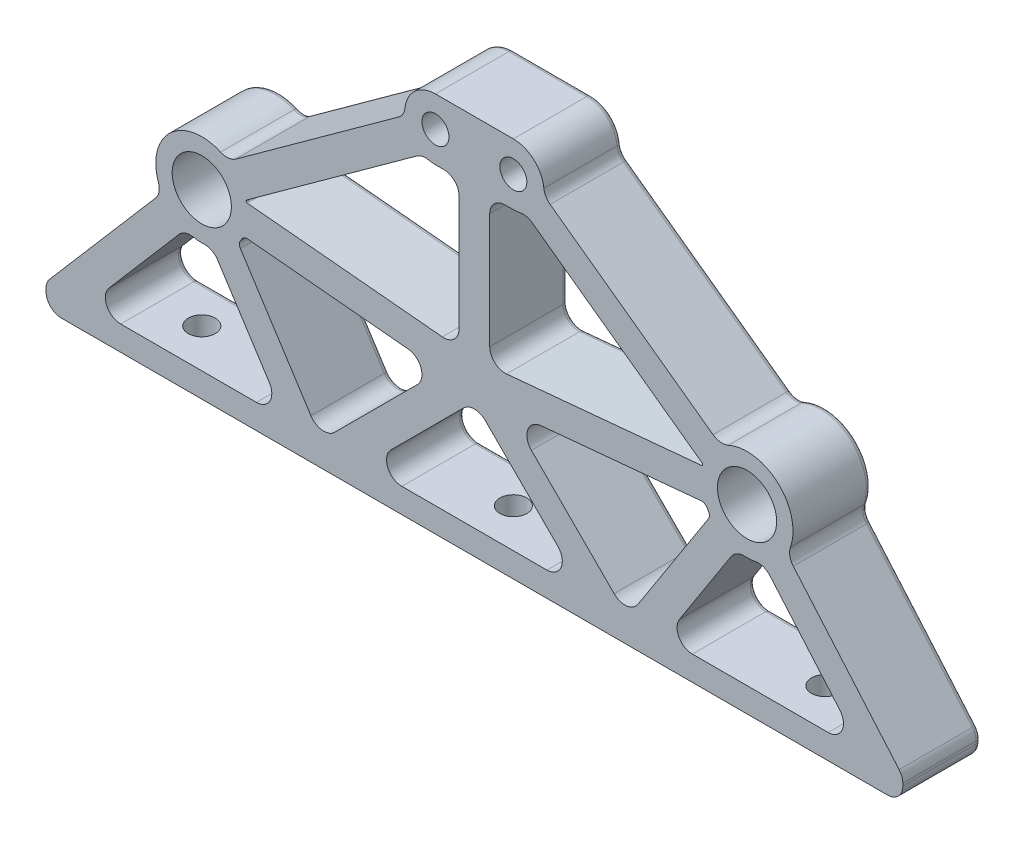
SolidWorks part; units mm, degrees
note: The reader was unsure of these and kept them because the rebuilt part matched: shared geometry of "Sketch3<3>".
ref_plane "Front Plane" through (0, 0, 0) normal (0, 0, 1) x (1, 0, 0)
ref_plane "Top Plane" through (0, 0, 0) normal (0, 1, 0) x (1, 0, 0)
ref_plane "Right Plane" through (0, 0, 0) normal (1, 0, 0) x (0, 0, -1)
sketch "Sketch1" plane through (0, 0, 0) normal (0, 0, 1) x (1, 0, 0)
  line L0 (0, 0) -> (60.4965, 0) construction
  circle A0 centre (0, 0) radius 25.4 construction
  circle A1 centre (44.45, 35.921) radius 31.75 construction
  circle A2 centre (133.35, 35.921) radius 31.75 construction
  circle A3 centre (177.8, 0) radius 25.4 construction
  circle A4 centre (222.25, 35.921) radius 31.75 construction
  circle A5 centre (311.15, 35.921) radius 31.75 construction
  circle A6 centre (355.6, 0) radius 25.4 construction
  circle A7 centre (0, 0) radius 50.8 construction
  circle A8 centre (355.6, 0) radius 50.8 construction
  circle A9 centre (177.8, 0) radius 50.8 construction
  circle A10 centre (88.9, 35.921) radius 12.7 construction
  circle A11 centre (266.7, 35.921) radius 12.7 construction
  point P20 (-50.8, 0)
  point P21 (406.4, 0)
  dimension "D1" = 50.8
  dimension "D2" = 63.5
  dimension "D4" = 101.6
  dimension "D5" = 25.4
  dimension "D6" = 25.4
  dimension "D3" = 355.6
  dimension "D7" = 177.8
  dimension "D8" = 177.8
  dimension "D9" = 457.2
  dimension "D10" = 44.45
sketch "Sketch2" plane through (0, 0, 0) normal (0, 0, 1) x (1, 0, 0)
  line L0 (-200000, 0) -> (200060.4965, 0) construction
  line L1 (-44.45, 6.35) -> (400.05, 6.35) construction
  line L2 (-44.45, 6.35) -> (-44.45, -19.05) construction
  line L3 (-44.45, -19.05) -> (400.05, -19.05) construction
  line L4 (400.05, 6.35) -> (400.05, -19.05) construction
  circle A0 centre (-38.1, 0) radius 2.25 construction
  circle A2 centre (-31.75, -6.35) radius 2.25 construction
  circle A3 centre (-25.4, 0) radius 2.25 construction
  circle A4 centre (-12.7, 0) radius 2.25 construction
  circle A5 centre (0, 0) radius 2.25 construction
  circle A6 centre (12.7, 0) radius 2.25 construction
  circle A7 centre (25.4, 0) radius 2.25 construction
  circle A8 centre (38.1, 0) radius 2.25 construction
  circle A9 centre (50.8, 0) radius 2.25 construction
  circle A10 centre (63.5, 0) radius 2.25 construction
  circle A11 centre (76.2, 0) radius 2.25 construction
  circle A12 centre (88.9, 0) radius 2.25 construction
  circle A13 centre (101.6, 0) radius 2.25 construction
  circle A14 centre (114.3, 0) radius 2.25 construction
  circle A15 centre (127, 0) radius 2.25 construction
  circle A16 centre (139.7, 0) radius 2.25 construction
  circle A17 centre (152.4, 0) radius 2.25 construction
  circle A18 centre (165.1, 0) radius 2.25 construction
  circle A19 centre (177.8, 0) radius 2.25 construction
  circle A20 centre (190.5, 0) radius 2.25 construction
  circle A21 centre (203.2, 0) radius 2.25 construction
  circle A22 centre (215.9, 0) radius 2.25 construction
  circle A23 centre (228.6, 0) radius 2.25 construction
  circle A24 centre (241.3, 0) radius 2.25 construction
  circle A25 centre (254, 0) radius 2.25 construction
  circle A26 centre (266.7, 0) radius 2.25 construction
  circle A27 centre (279.4, 0) radius 2.25 construction
  circle A28 centre (292.1, 0) radius 2.25 construction
  circle A29 centre (304.8, 0) radius 2.25 construction
  circle A30 centre (317.5, 0) radius 2.25 construction
  circle A31 centre (330.2, 0) radius 2.25 construction
  circle A32 centre (342.9, 0) radius 2.25 construction
  circle A33 centre (355.6, 0) radius 2.25 construction
  circle A34 centre (368.3, 0) radius 2.25 construction
  circle A35 centre (381, 0) radius 2.25 construction
  circle A36 centre (393.7, 0) radius 2.25 construction
  circle A37 centre (-25.4, -12.7) radius 2.25 construction
  circle A38 centre (-12.7, -12.7) radius 2.25 construction
  circle A39 centre (0, -12.7) radius 2.25 construction
  circle A40 centre (12.7, -12.7) radius 2.25 construction
  circle A41 centre (25.4, -12.7) radius 2.25 construction
  circle A42 centre (38.1, -12.7) radius 2.25 construction
  circle A43 centre (50.8, -12.7) radius 2.25 construction
  circle A44 centre (63.5, -12.7) radius 2.25 construction
  circle A45 centre (76.2, -12.7) radius 2.25 construction
  circle A46 centre (88.9, -12.7) radius 2.25 construction
  circle A47 centre (101.6, -12.7) radius 2.25 construction
  circle A48 centre (114.3, -12.7) radius 2.25 construction
  circle A49 centre (127, -12.7) radius 2.25 construction
  circle A50 centre (139.7, -12.7) radius 2.25 construction
  circle A51 centre (152.4, -12.7) radius 2.25 construction
  circle A52 centre (165.1, -12.7) radius 2.25 construction
  circle A53 centre (177.8, -12.7) radius 2.25 construction
  circle A54 centre (190.5, -12.7) radius 2.25 construction
  circle A55 centre (203.2, -12.7) radius 2.25 construction
  circle A56 centre (215.9, -12.7) radius 2.25 construction
  circle A57 centre (228.6, -12.7) radius 2.25 construction
  circle A58 centre (241.3, -12.7) radius 2.25 construction
  circle A59 centre (254, -12.7) radius 2.25 construction
  circle A60 centre (266.7, -12.7) radius 2.25 construction
  circle A61 centre (279.4, -12.7) radius 2.25 construction
  circle A62 centre (292.1, -12.7) radius 2.25 construction
  circle A63 centre (304.8, -12.7) radius 2.25 construction
  circle A64 centre (317.5, -12.7) radius 2.25 construction
  circle A65 centre (330.2, -12.7) radius 2.25 construction
  circle A66 centre (342.9, -12.7) radius 2.25 construction
  circle A67 centre (355.6, -12.7) radius 2.25 construction
  circle A68 centre (368.3, -12.7) radius 2.25 construction
  circle A69 centre (381, -12.7) radius 2.25 construction
  circle A70 centre (393.7, -12.7) radius 2.25 construction
  circle A71 centre (-38.1, -12.7) radius 2.25 construction
  circle A72 centre (-19.05, -6.35) radius 2.25 construction
  circle A73 centre (-6.35, -6.35) radius 2.25 construction
  circle A74 centre (6.35, -6.35) radius 2.25 construction
  circle A75 centre (19.05, -6.35) radius 2.25 construction
  circle A76 centre (31.75, -6.35) radius 2.25 construction
  circle A77 centre (44.45, -6.35) radius 2.25 construction
  circle A78 centre (57.15, -6.35) radius 2.25 construction
  circle A79 centre (69.85, -6.35) radius 2.25 construction
  circle A80 centre (82.55, -6.35) radius 2.25 construction
  circle A81 centre (95.25, -6.35) radius 2.25 construction
  circle A82 centre (107.95, -6.35) radius 2.25 construction
  circle A83 centre (120.65, -6.35) radius 2.25 construction
  circle A84 centre (133.35, -6.35) radius 2.25 construction
  circle A85 centre (146.05, -6.35) radius 2.25 construction
  circle A86 centre (158.75, -6.35) radius 2.25 construction
  circle A87 centre (171.45, -6.35) radius 2.25 construction
  circle A88 centre (184.15, -6.35) radius 2.25 construction
  circle A89 centre (196.85, -6.35) radius 2.25 construction
  circle A90 centre (209.55, -6.35) radius 2.25 construction
  circle A91 centre (222.25, -6.35) radius 2.25 construction
  circle A92 centre (234.95, -6.35) radius 2.25 construction
  circle A93 centre (247.65, -6.35) radius 2.25 construction
  circle A94 centre (260.35, -6.35) radius 2.25 construction
  circle A95 centre (273.05, -6.35) radius 2.25 construction
  circle A96 centre (285.75, -6.35) radius 2.25 construction
  circle A97 centre (298.45, -6.35) radius 2.25 construction
  circle A98 centre (311.15, -6.35) radius 2.25 construction
  circle A99 centre (323.85, -6.35) radius 2.25 construction
  circle A100 centre (336.55, -6.35) radius 2.25 construction
  circle A101 centre (349.25, -6.35) radius 2.25 construction
  circle A102 centre (361.95, -6.35) radius 2.25 construction
  circle A103 centre (374.65, -6.35) radius 2.25 construction
  circle A104 centre (387.35, -6.35) radius 2.25 construction
  dimension "D5" = 4.5
  dimension "D1" = 25.4
  dimension "D2" = 444.5
  dimension "D3" = 6.35
  dimension "D4" = 44.45
  dimension "D6" = 6.35
  dimension "D7" = 6.35
  dimension "D8" = 6.35
  dimension "D12" = 12.7
  dimension "D9" = 35
  dimension "D10" = 2
  dimension "D11" = 34
sketch "Sketch3" plane through (0, 0, 0) normal (0, 0, 1) x (1, 0, 0)
  line L0 (44.45, 35.921) -> (88.9, 31.75) construction
  line L1 (88.9, 31.75) -> (133.35, 35.921) construction
  line L2 (44.45, 35.921) -> (19.05, 6.35) construction
  line L3 (-44.45, 6.35) -> (400.05, 6.35) construction
  line L4 (19.05, 6.35) -> (158.75, 6.35) construction
  line L5 (158.75, 6.35) -> (133.35, 35.921) construction
  line L6 (44.45, 35.921) -> (63.5, 6.35) construction
  line L7 (63.5, 6.35) -> (88.9, 31.75) construction
  line L8 (88.9, 31.75) -> (114.3, 6.35) construction
  line L9 (114.3, 6.35) -> (133.35, 35.921) construction
  line L10 (19.05, 6.35) -> (158.75, 6.35)
  line L11 (158.75, 6.35) -> (158.75, 10.1868)
  line L12 (158.75, 10.1868) -> (139.8538, 32.186)
  line L13 (88.9, 34.261) -> (126.0763, 37.7495)
  line L14 (126.5434, 32.7713) -> (94.4278, 29.7577)
  line L15 (152.0186, 10.35) -> (119.8507, 10.35)
  line L16 (119.8507, 10.35) -> (131.6222, 28.6228)
  line L17 (152.0186, 10.35) -> (136.0609, 28.9281)
  line L18 (113.8766, 10.309) -> (127.4189, 31.3306)
  line L19 (113.8766, 10.309) -> (94.4278, 29.7577)
  line L20 (106.7645, 10.35) -> (71.0355, 10.35)
  line L21 (71.0355, 10.35) -> (88.9, 28.2145)
  line L22 (106.7645, 10.35) -> (88.9, 28.2145)
  line L24 (51.2566, 32.7713) -> (83.3722, 29.7577)
  line L26 (25.7814, 10.35) -> (57.9493, 10.35)
  line L27 (57.9493, 10.35) -> (46.1778, 28.6228)
  line L28 (25.7814, 10.35) -> (41.7391, 28.9281)
  line L29 (19.05, 6.35) -> (19.05, 10.1868)
  line L30 (19.05, 10.1868) -> (37.9462, 32.186)
  line L31 (51.7237, 37.7495) -> (88.9, 34.261)
  line L32 (63.9234, 10.309) -> (50.3811, 31.3306)
  line L33 (63.9234, 10.309) -> (83.3722, 29.7577)
  circle A0 centre (44.45, 35.921) radius 4.826
  circle A2 centre (133.35, 35.921) radius 4.826
  circle A3 centre (44.45, 35.921) radius 7.5
  circle A5 centre (133.35, 35.921) radius 7.5
  circle A6 centre (44.45, 35.921) radius 2.5
  circle A7 centre (133.35, 35.921) radius 2.5
  dimension "D1" = 9.652
  dimension "D2" = 15
  dimension "D3" = 5
  dimension "D20" = 5
  dimension "Thickness" = 5
  dimension "D4" = 2.5
  dimension "D5" = 2.5
  dimension "D6" = 5
  dimension "D7" = 2.5
  dimension "D8" = 5
  dimension "D9" = 2.5
  dimension "D10" = 5
  dimension "D11" = 5
  dimension "D12" = 2.5
  dimension "D13" = 4
  dimension "D14" = 2.5
  dimension "D15" = 5
  dimension "D16" = 5
  dimension "D17" = 5
  dimension "D18" = 2.5
  dimension "D19" = 25.4
extrude "Boss-Extrude1" add sketch "Sketch3" along normal blind 12.7 contours A5 L13 L31 A3 L24 L33 L32 L27 L26 L28 L30 L29 L10 L11 L12 L17 L15 L16 L18 L19 L14 L22 L20 L21 | A3 A0 | A5 A2
sketch "Sketch5" plane through (0, 0, 0) normal (0, 0, -1) x (-1, 0, 0)
  line L0 (-88.9, 34.261) -> (-88.9, 11.7037) construction
  line L1 (-95.25, 63.5) -> (-82.55, 63.5) construction
  line L2 (-95.25, 68.5) -> (-82.55, 68.5)
  line L3 (-95.25, 58.5) -> (-82.55, 58.5)
  line L4 (-19.05, 6.35) -> (-158.75, 6.35) construction
  line L5 (-51.7237, 37.7495) -> (-88.9, 34.261) construction
  line L6 (-88.9, 34.261) -> (-126.0763, 37.7495) construction
  line L7 (-51.7237, 37.7495) -> (-88.9, 34.261)
  line L8 (-88.9, 34.261) -> (-126.0763, 37.7495)
  line L9 (-91.4, 34.4956) -> (-91.4, 58.5)
  line L10 (-86.4, 34.4956) -> (-86.4, 58.5)
  line L11 (-126.1562, 38.0421) -> (-97.2917, 58.9359)
  line L12 (-129.088, 42.0923) -> (-100.2235, 62.9861)
  line L13 (-80.5083, 58.9359) -> (-51.6438, 38.0421)
  line L14 (-48.712, 42.0923) -> (-77.5765, 62.9861)
  line L15 (-133.35, 35.921) -> (-95.25, 63.5) construction
  line L16 (-82.55, 63.5) -> (-44.45, 35.921) construction
  arc A2 (-37.9462, 32.186) -> (-51.7237, 37.7495) centre (-44.45, 35.921) ccw construction
  arc A3 (-126.0763, 37.7495) -> (-139.8538, 32.186) centre (-133.35, 35.921) ccw construction
  arc A4 (-37.9462, 32.186) -> (-51.7237, 37.7495) centre (-44.45, 35.921) ccw
  arc A5 (-126.0763, 37.7495) -> (-139.8538, 32.186) centre (-133.35, 35.921) ccw
  arc A6 (-95.25, 68.5) -> (-95.25, 58.5) centre (-95.25, 63.5) ccw
  arc A7 (-82.55, 58.5) -> (-82.55, 68.5) centre (-82.55, 63.5) ccw
  circle A8 centre (-95.25, 63.5) radius 2.2
  circle A9 centre (-82.55, 63.5) radius 2.2
  point P0 (-88.9, 34.261)
  point P3 (-133.35, 35.921)
  point P4 (-44.45, 35.921)
  point P5 (-88.9, 63.5)
  point P10 (-88.9, 6.35)
  dimension "D5" = 10
  dimension "D6" = 57.15
  dimension "D7" = 4.4
  dimension "D1" = 12.7
  dimension "D2" = 5
  dimension "D3" = 5
  dimension "D4" = 5
extrude "Boss-Extrude3" add sketch "Sketch5" against normal blind 12.7
fillet "Fillet1" radius 2.5 31 edges at (158.75, 6.35, 6.35) (158.75, 10.1868, 6.35) (19.05, 6.35, 6.35) (19.05, 10.1868, 6.35) (139.8538, 32.186, 6.35) (152.0186, 10.35, 6.35) (136.0609, 28.9281, 6.35) (131.6222, 28.6228, 6.35) (119.8507, 10.35, 6.35) (113.8766, 10.309, 6.35) (106.7645, 10.35, 6.35) (25.7814, 10.35, 6.35) (41.7391, 28.9281, 6.35) (46.1778, 28.6228, 6.35) (57.9493, 10.35, 6.35) (71.0355, 10.35, 6.35) (63.9234, 10.309, 6.35) (37.9462, 32.186, 6.35) (88.9, 28.2145, 6.35) (94.4278, 29.7577, 6.35) (83.3722, 29.7577, 6.35) (91.4, 34.4956, 6.35) (86.4, 34.4956, 6.35) (129.088, 42.0923, 6.35) (48.712, 42.0923, 6.35) (100.2235, 62.9861, 6.35) (77.5765, 62.9861, 6.35) (80.5083, 58.9359, 6.35) (86.4, 58.5, 6.35) (91.4, 58.5, 6.35) (97.2917, 58.9359, 6.35)
fillet "Fillet5" radius 0.2 4 edges at (126.0763, 37.7495, 6.35) (126.1562, 38.0421, 6.35) (51.7237, 37.7495, 6.35) (51.6438, 38.0421, 6.35)
fillet "Fillet6" radius 1 4 edges at (50.3811, 31.3306, 6.35) (51.2566, 32.7713, 6.35) (126.5434, 32.7713, 6.35) (127.4189, 31.3306, 6.35)
sketch "Sketch4" plane through (0, 6.35, 0) normal (0, -1, 0) x (1, 0, 0)
  line L0 (21.55, 12.7) -> (21.55, 0) construction
  circle A0 centre (38.1, 6.35) radius 2.2
  circle A1 centre (88.9, 6.35) radius 2.2
  circle A2 centre (139.7, 6.35) radius 2.2
  point P0 (139.7, 0)
  point P2 (88.9, 0)
  point P4 (38.1, 0)
  point P15 (21.55, 6.35)
  dimension "D1" = 4.4
extrude "Cut-Extrude1" cut sketch "Sketch4" against normal up to next
extrude "Boss-Extrude2" add sketch "Sketch3<3>" along normal blind 3.175 contours A0 | A2
sketch "Sketch3<3>" plane through (0, 0, 0) normal (0, 0, 1) x (1, 0, 0) same geometry as "Sketch3"
fillet "Fillet2" radius 0.75 86 edges at (135.85, 35.921, 0) (46.95, 35.921, 0) (74.7614, 11.8933, 0) (81.2178, 20.5322, 0) (88.9, 27.1789, 0) (96.5822, 20.5322, 0) (103.0386, 11.8933, 0) (88.9, 10.35, 0) (136.0279, 28.4526, 0) (142.7842, 21.1008, 0) (148.8474, 11.8065, 0) (135.5053, 10.35, 0) (122.2402, 11.6531, 0) (126.5475, 20.7453, 0) (131.7201, 28.1562, 0) (133.8647, 28.4387, 0) (46.0799, 28.1562, 0) (51.2525, 20.7453, 0) (55.5598, 11.6531, 0) (42.2947, 10.35, 0) (28.9526, 11.8065, 0) (35.0158, 21.1008, 0) (41.7721, 28.4526, 0) (43.9353, 28.4387, 0) (65.0032, 31.4814, 0) (80.1963, 28.6131, 0) (72.8634, 19.2489, 0) (64.081, 11.7821, 0) (56.4959, 21.8386, 0) (158.5943, 10.1291, 0) (149.5179, 20.935, 0) (140.3289, 32.1469, 0) (138.4284, 41.4401, 0) (110.0352, 36.2442, 0) (67.7648, 36.2442, 0) (39.3716, 41.4401, 0) (37.4711, 32.1469, 0) (28.2821, 20.935, 0) (19.2057, 10.1291, 0) (19.05, 9.0553, 0) (19.7822, 7.0822, 0) (88.9, 6.35, 0) (158.0178, 7.0822, 0) (158.75, 9.0553, 0) (121.3041, 21.8386, 0) (113.719, 11.7821, 0) (104.9366, 19.2489, 0) (97.6037, 28.6131, 0) (112.7968, 31.4814, 0) (86.4, 46.6206, 0) (65.6224, 48.1606, 0) (114.5224, 52.6357, 0) (63.2776, 52.6357, 0) (112.1776, 48.1606, 0) (91.4, 46.6206, 0) (85.5832, 35.3926, 0) (129.0096, 42.5625, 0) (48.7904, 42.5625, 0) (92.2168, 35.3926, 0) (93.05, 63.5, 0) (80.35, 63.5, 0) (83.225, 58.5, 0) (88.9, 68.5, 0) (79.2015, 67.2131, 0) (95.7852, 58.5287, 0) (80.4421, 58.619, 0) (82.0148, 58.5287, 0) (85.6678, 57.7678, 0) (100.5452, 63.0222, 0) (98.5985, 67.2131, 0) (77.2548, 63.0222, 0) (92.1322, 57.7678, 0) (94.575, 58.5, 0) (97.3579, 58.619, 0) (50.5872, 31.3057, 0) (50.8594, 32.0263, 0) (51.3736, 32.5998, 0) (51.6858, 38.0285, 0) (51.753, 37.7825, 0) (51.6852, 37.8962, 0) (127.2128, 31.3057, 0) (126.4264, 32.5998, 0) (126.9406, 32.0263, 0) (126.1142, 38.0285, 0) (126.1148, 37.8962, 0) (126.047, 37.7825, 0)
